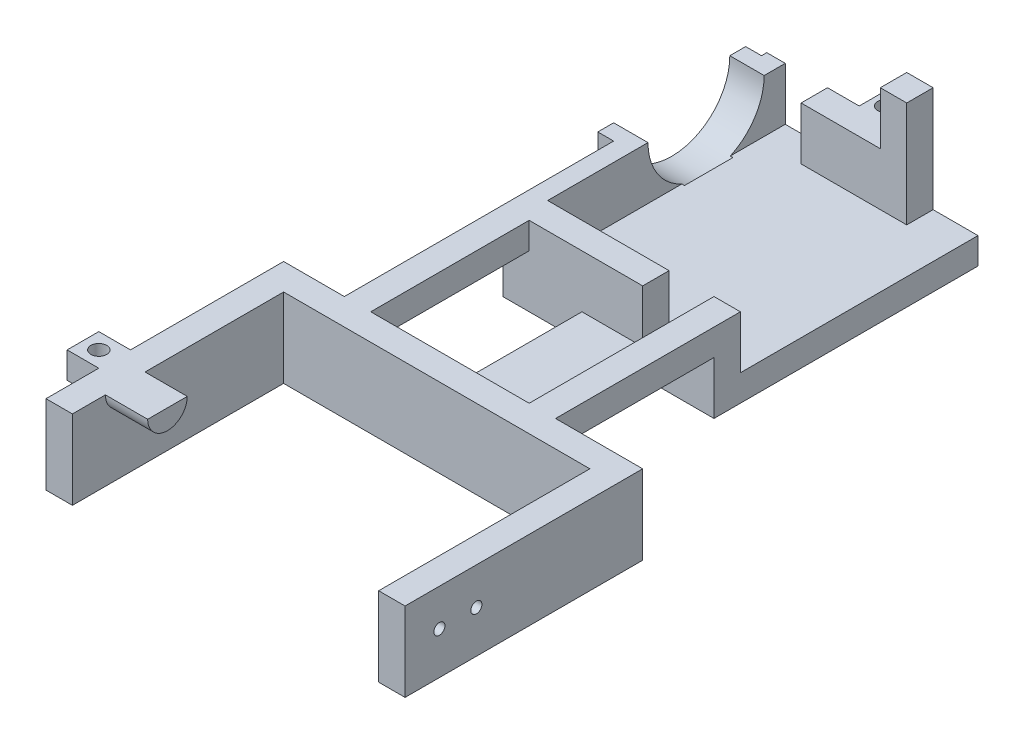
SolidWorks part; units mm, degrees
ref_plane "Front Plane" through (0, 0, 0) normal (0, 0, 1) x (1, 0, 0)
ref_plane "Top Plane" through (0, 0, 0) normal (0, 1, 0) x (1, 0, 0)
ref_plane "Right Plane" through (0, 0, 0) normal (1, 0, 0) x (0, 0, -1)
sketch "Sketch1" plane through (0, 0, 0) normal (0, 1, 0) x (1, 0, 0)
  line L1 (-20, 25) -> (20, 25)
  line L2 (-20, 25) -> (-20, -25)
  line L3 (-20, -25) -> (20, -25)
  line L4 (20, 25) -> (20, -25)
  point P6 (20, 0)
  point P7 (0, 25)
  dimension "D1" = 40
  dimension "D2" = 50
extrude "Boss-Extrude1" add sketch "Sketch1" along normal blind 5
sketch "Sketch3" plane through (0, 5, 0) normal (0, 1, 0) x (1, 0, 0)
  line L0 (20, 25) -> (-20, 25) construction
  line L1 (-8.5, 25) -> (6.5, 25)
  line L2 (-8.5, 25) -> (-8.5, 20)
  line L3 (-8.5, 20) -> (6.5, 20)
  line L4 (6.5, 25) -> (6.5, 20)
  line L5 (20, -25) -> (20, 25) construction
  line L6 (-20, -25) -> (20, -25) construction
  line L7 (-20, 25) -> (-16.5, 25)
  line L10 (-16.5, 25) -> (-16.5, -20)
  line L11 (20, -25) -> (15, -25)
  line L12 (20, -25) -> (20, -20)
  line L13 (20, -20) -> (15, -20)
  line L14 (15, -25) -> (15, -20)
  line L15 (6.5, -25) -> (-20, -25)
  line L16 (6.5, -25) -> (6.5, -20)
  line L17 (6.5, -20) -> (-16.5, -20)
  line L20 (16, 25) -> (16, 20) construction
  line L21 (16, 20) -> (20, 20) construction
  line L22 (-20, 25) -> (-20, -25)
  line L23 (6.5, -20) -> (11.5, -20) construction
  line L24 (11.5, -20) -> (11.5, -25) construction
  line L26 (6.5, 20) -> (11.5, 20)
  line L27 (6.5, 20) -> (6.5, 25)
  line L28 (6.5, 25) -> (11.5, 25)
  line L29 (11.5, 20) -> (11.5, 25)
  line M17 (-20, 25) -> (-20, -25)
  line M18 (-20, -25) -> (20, -25)
  line M20 (20, 25) -> (-20, 25)
  dimension "D1" = 8
  dimension "D2" = 15
  dimension "D3" = 3.5
  dimension "D4" = 5
  dimension "D5" = 5
  dimension "D7" = 5
  dimension "D8" = 4
  dimension "D9" = 5
extrude "Boss-Extrude5" add sketch "Sketch3" along normal blind 20 contours L26 L29 L4 M20 region at (9, 5, -22.5)
extrude "Boss-Extrude6" add sketch "Sketch3<3>" along normal blind 10 contours L4 L2 L3 M20 | L16 L17 L10 M20 M17 M18 | L12 L11 L14 L13 region at (-1, 5, -22.5) region at (-17.0659, 5, -2.5)
sketch "Sketch3<3>" plane through (0, 5, 0) normal (0, 1, 0) x (1, 0, 0) same geometry as "Sketch3"
sketch "Sketch8" plane through (-20, 0, 0) normal (-1, 0, 0) x (0, 0, 1)
  line L0 (-25, 15) -> (25, 15) construction
  line L1 (1, 15) -> (-21, 15)
  arc A0 (-21, 15) -> (1, 15) centre (-10, 15) ccw
  point P1 (0, 0)
  dimension "D1" = 22
extrude "Cut-Extrude3" cut sketch "Sketch8" against normal blind 4
sketch "Sketch11" plane through (0, 0, -25) normal (0, 0, -1) x (-1, 0, 0)
  line L0 (-6.5, 15) -> (8.5, 15) construction
  line L1 (2.5, 10) -> (-2.5, 10)
  line L2 (2.5, 10) -> (2.5, 15)
  line L3 (2.5, 15) -> (-2.5, 15)
  line L4 (-2.5, 10) -> (-2.5, 15)
  point P6 (0, 10)
  dimension "D1" = 5
  dimension "D2" = 5
extrude "Boss-Extrude10" add sketch "Sketch11" along normal blind 5
sketch "Sketch12" plane through (0, 10, 0) normal (0, -1, 0) x (1, 0, 0)
  line L0 (-2.5, -30) -> (-2.5, -25) construction
  line L1 (20, -25) -> (-20, -25) construction
  circle A0 centre (0, -27.5) radius 1.5
  point P5 (-2.5, -27.5)
  point P8 (0, -25)
  dimension "D1" = 3
extrude "Cut-Extrude4" cut sketch "Sketch12" against normal blind 5
sketch "Sketch14" plane through (0, 0, 25) normal (0, 0, 1) x (1, 0, 0)
  line L0 (15, 15) -> (15, 5) construction
  line L5 (-20, 0) -> (20, 0) construction
  line L10 (-5, 0) -> (5, 0)
  line L11 (-5, 0) -> (-5, 5)
  line L12 (-5, 5) -> (5, 5)
  line L13 (5, 0) -> (5, 5)
  line L14 (-20, 15) -> (-15, 15)
  line L15 (-20, 15) -> (-20, 10)
  line L16 (-20, 10) -> (-15, 10)
  line L17 (-15, 15) -> (-15, 10)
  line L18 (20, 15) -> (15, 15)
  line L19 (20, 15) -> (20, 10)
  line L20 (20, 10) -> (15, 10)
  line L21 (15, 15) -> (15, 10)
  point P18 (0, 5)
  dimension "D1" = 5
  dimension "D2" = 5
  dimension "D3" = 10
  dimension "D4" = 5
  dimension "D5" = 5
extrude "Boss-Extrude12" add sketch "Sketch14" along normal blind 30
sketch "Sketch15" plane through (0, 0, 55) normal (0, 0, 1) x (1, 0, 0)
  line L0 (-5, 0) -> (5, 0) construction
  line L1 (20, 0) -> (-20, 0)
  line L2 (20, 0) -> (20, 15)
  line L3 (20, 15) -> (-20, 15)
  line L4 (-20, 0) -> (-20, 15)
  point P4 (0, 0)
  point P6 (0, 0)
  dimension "D1" = 40
  dimension "D2" = 15
extrude "Boss-Extrude13" add sketch "Sketch15" along normal blind 5
sketch "Sketch16" plane through (20, 0, 0) normal (1, 0, 0) x (0, 0, -1)
  line L0 (-60, 15) -> (-20, 15) construction
  line L1 (-55, 0) -> (-60, 0)
  line L2 (-55, 0) -> (-55, 15)
  line L3 (-55, 15) -> (-60, 15)
  line L4 (-60, 0) -> (-60, 15)
  line L7 (-60, 0) -> (-55, 0) construction
  line L8 (-55, 0) -> (-55, 5) construction
  line L9 (-60, 0) -> (-60, 15) construction
  line M13 (-20, 15) -> (-60, 15)
  line M14 (-60, 15) -> (-60, 0)
  line M15 (-60, 0) -> (-55, 0)
  line M16 (-55, 0) -> (-55, 10)
extrude "Boss-Extrude15" add sketch "Sketch16" along normal blind 16.5 contours L2 M16 M13 M14 M15 region at (20, 7.5, 57.5)
sketch "Sketch17" plane through (-20, 0, 0) normal (-1, 0, 0) x (0, 0, 1)
  line L1 (60, 0) -> (55, 0)
  line L2 (60, 0) -> (60, 15)
  line L3 (60, 15) -> (55, 15)
  line L4 (55, 0) -> (55, 15)
  line L5 (55, 10) -> (55, 0) construction
  line L6 (60, 15) -> (1, 15) construction
  line L7 (60, 0) -> (55, 0) construction
  line L8 (60, 15) -> (60, 0) construction
  line M13 (55, 10) -> (55, 0)
  line M14 (55, 0) -> (60, 0)
  line M15 (60, 0) -> (60, 15)
  line M16 (60, 15) -> (1, 15)
extrude "Boss-Extrude17" add sketch "Sketch17" along normal blind 11.5 contours L4 M13 M14 M15 M16 region at (-20, 7.5, 57.5)
sketch "Sketch18" plane through (0, 0, 60) normal (0, 0, 1) x (1, 0, 0)
  line L0 (36.5, 15) -> (-31.5, 15) construction
  line L1 (36.5, 0) -> (31.5, 0)
  line L2 (36.5, 0) -> (36.5, 15)
  line L3 (36.5, 15) -> (31.5, 15)
  line L4 (31.5, 0) -> (31.5, 15)
  line L6 (-31.5, 0) -> (-26.5, 0)
  line L7 (-31.5, 0) -> (-31.5, 15)
  line L8 (-31.5, 15) -> (-26.5, 15)
  line L9 (-26.5, 0) -> (-26.5, 15)
  dimension "D1" = 5
extrude "Boss-Extrude18" add sketch "Sketch18" along normal blind 40
sketch "Sketch19" plane through (-26.5, 0, 0) normal (1, 0, 0) x (0, 0, -1)
  line L1 (-86.25, 15) -> (-93.75, 15)
  line L2 (-100, 15) -> (-60, 15) construction
  arc A0 (-93.75, 15) -> (-86.25, 15) centre (-90, 15) ccw
  dimension "D1" = 7.5
  dimension "D2" = 10
extrude "Boss-Extrude19" add sketch "Sketch19" along normal blind 8
sketch "Sketch20" plane through (-31.5, 0, 0) normal (-1, 0, 0) x (0, 0, 1)
  line L1 (84, 15) -> (90, 15)
  line L2 (84, 15) -> (84, 10)
  line L3 (84, 10) -> (90, 10)
  line L4 (90, 15) -> (90, 10)
  line L5 (100, 15) -> (100, 0) construction
  line L6 (100, 15) -> (55, 15) construction
  dimension "D1" = 5
  dimension "D2" = 6
  dimension "D3" = 10
extrude "Boss-Extrude20" add sketch "Sketch20" along normal blind 6
sketch "Sketch21" plane through (0, 10, 0) normal (0, -1, 0) x (1, 0, 0)
  line L0 (-37.5, 84) -> (-37.5, 90) construction
  line L1 (-37.5, 84) -> (-31.5, 84) construction
  circle A0 centre (-34.5, 87) radius 1.5
  point P4 (-37.5, 87)
  point P7 (-34.5, 84)
  dimension "D1" = 3
extrude "Cut-Extrude5" cut sketch "Sketch21" against normal blind 5
sketch "Sketch24" plane through (31.5, 0, 0) normal (-1, 0, 0) x (0, 0, 1)
  line L0 (90, 15) -> (97, 15) construction
  line L1 (100, 15) -> (60, 15) construction
  line L2 (90, 15) -> (83, 15) construction
  line L3 (86.5, 8) -> (93.5, 8) construction
  circle A0 centre (93.5, 8) radius 1.05
  circle A1 centre (86.5, 8) radius 1.05
  dimension "D7" = 2.1
  dimension "D1" = 7
  dimension "D2" = 7
  dimension "D3" = 7
  dimension "D4" = 7
  dimension "D5" = 3
extrude "Cut-Extrude7" cut sketch "Sketch24" against normal blind 5
sketch "Sketch25" plane through (-20, 0, 0) normal (-1, 0, 0) x (0, 0, 1)
  line L0 (-21, 15) -> (-24, 15)
  line L1 (-24, 15) -> (-24, 0)
  line L2 (-24, 0) -> (4, 0)
  line L3 (-25, 0) -> (25, 0) construction
  line L4 (4, 0) -> (4, 15)
  line L5 (1, 15) -> (55, 15) construction
  line L6 (4, 15) -> (1, 15)
  arc A0 (-21, 15) -> (1, 15) centre (-10, 15) ccw
  point P15 (0, 0)
  point P16 (-24, 4.2184)
  point P17 (0, 0)
  dimension "D1" = 3
extrude "Boss-Extrude21" add sketch "Sketch25" along normal blind 3
